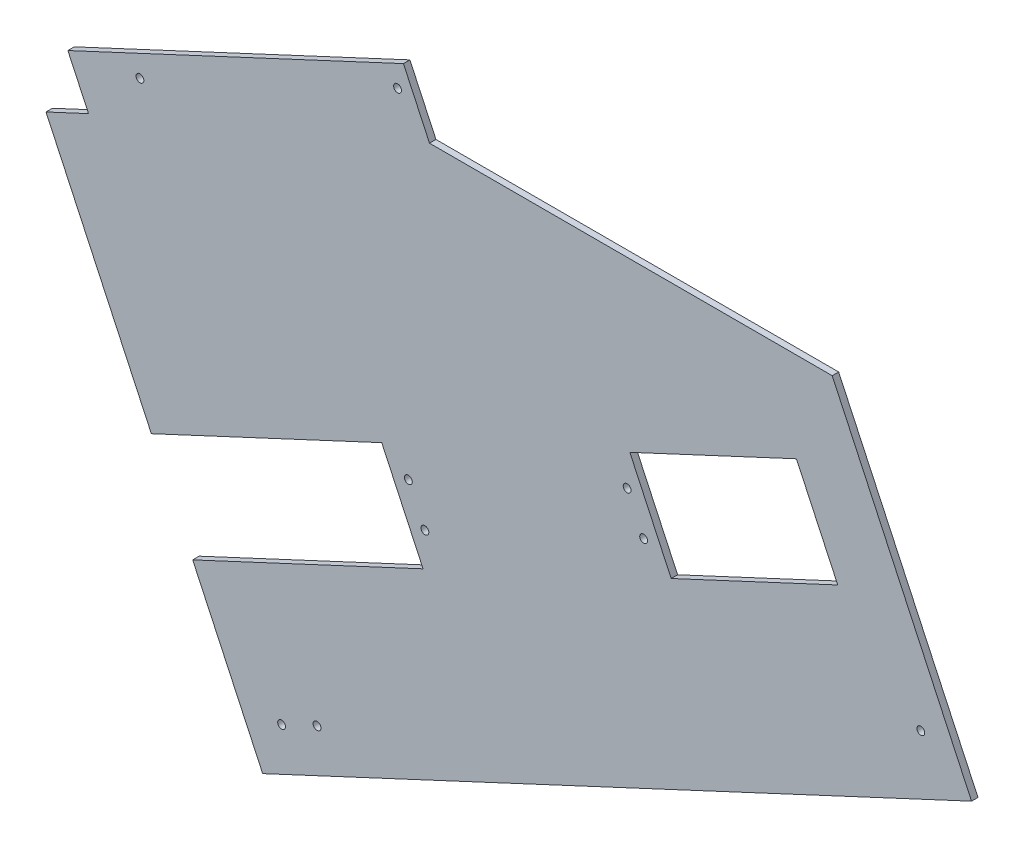
SolidWorks part; units mm, degrees
material "Balsa"
ref_plane "Front Plane" through (0, 0, 0) normal (0, 0, 1) x (1, 0, 0)
ref_plane "Top Plane" through (0, 0, 0) normal (0, 1, 0) x (1, 0, 0)
ref_plane "Right Plane" through (0, 0, 0) normal (1, 0, 0) x (0, 0, -1)
sketch "Sketch1" plane through (0, 0, 0) normal (0, 0, 1) x (1, 0, 0)
  line L0 (327.4362, 0.0035) -> (121.4984, 0.0035)
  line L1 (121.4984, 0.0035) -> (108.169, 28.5884)
  line L2 (108.169, 28.5884) -> (-63.4467, -51.4373)
  line L3 (-63.4467, -51.4373) -> (57.9293, -311.7289) construction
  line L4 (57.9293, -311.7289) -> (398.701, -152.8244)
  line L5 (271.5352, 119.8836) -> (277.3251, 107.4672) construction
  line L6 (190.5834, 136.311) -> (-12.0446, 41.824) construction
  line L7 (-63.4467, -51.4373) -> (255.5737, 97.3243) construction
  line L8 (398.701, -152.8244) -> (327.4362, 0.0035)
  line L9 (57.9293, -311.7289) -> (36.1779, -321.8717)
  line L10 (36.1779, -321.8717) -> (-74.6326, -84.2378)
  line L11 (50.7481, 0) -> (323.7481, 0) construction
  line L12 (-74.6326, -84.2378) -> (-52.8812, -74.095)
  line L13 (-90.9879, -49.1637) -> (-85.1981, -61.5801) construction
  line L14 (-52.8812, -74.095) -> (-63.4467, -51.4373)
  circle A0 centre (162.7613, -40.6644) radius 32.5 construction
  circle A1 centre (336.0773, -108.8767) radius 32.5 construction
  circle A2 centre (90.1802, -40.6644) radius 32.5 construction
  circle A3 centre (232.5481, -40.6644) radius 32.5 construction
  circle A4 centre (207.2768, 100.5118) radius 39.5 construction
  arc A5 (-3.3339, 41.4724) -> (-17.3744, 34.9252) centre (-8.0297, 33.2141) ccw construction
  circle A6 centre (304.5287, -40.6644) radius 32.5 construction
  circle A7 centre (254.9584, -108.8767) radius 32.5 construction
  circle A8 centre (179.3206, -108.8767) radius 32.5 construction
  circle A9 centre (101.4264, -108.8767) radius 32.5 construction
  circle A10 centre (270.383, -163.8108) radius 32.5 construction
  circle A11 centre (372.7594, -134.5783) radius 2
  dimension "D2" = 65
  dimension "D3" = 65
  dimension "D5" = 4
  dimension "D1" = 350
  dimension "D4" = 25
  dimension "24.5/2" = 15.8
  dimension "D6" = 27.5
extrude "Boss-Extrude1" add sketch "Sketch1" along normal up to surface (3.3 mm away)
sketch "Sketch2" plane through (0, 0, 3.3) normal (0, 0, 1) x (1, 0, 0)
  circle A0 centre (105.1447, 16.1444) radius 2
  circle A1 centre (-26.5934, -45.2861) radius 2
  circle A2 centre (-26.5934, -45.2861) radius 2 construction
  circle A3 centre (105.1447, 16.1444) radius 2 construction
extrude "Cut-Extrude1" cut sketch "Sketch2" against normal through all
sketch "Sketch3" plane through (0, 0, 3.3) normal (0, 0, 1) x (1, 0, 0)
  line L2 (398.701, -152.8244) -> (36.1779, -321.8717) construction
  line L3 (36.1779, -321.8717) -> (-74.6326, -84.2378) construction
  circle A0 centre (45.8517, -295.2932) radius 2
  circle A1 centre (63.9779, -286.8408) radius 2
  dimension "D1" = 4
  dimension "D2" = 4
  dimension "D3" = 20
  dimension "D5" = 20
  dimension "D6" = 20
  dimension "D4" = 20
extrude "Cut-Extrude2" cut sketch "Sketch3" against normal blind 4
sketch "Sketch4" plane through (0, 0, 3.3) normal (0, 0, 1) x (1, 0, 0)
  line L0 (330.2782, -91.2744) -> (309.1473, -45.959)
  line L1 (309.1473, -45.959) -> (223.9543, -85.6851)
  line L2 (223.9543, -85.6851) -> (245.0853, -131.0005)
  line L3 (245.0853, -131.0005) -> (330.2782, -91.2744)
  line L4 (309.1473, -45.959) -> (223.9543, -85.6851) construction
  line L5 (245.0853, -131.0005) -> (330.2782, -91.2744) construction
  line L6 (330.2782, -91.2744) -> (309.1473, -45.959) construction
  line L7 (118.2022, -190.1671) -> (97.0712, -144.8517)
  line L8 (97.0712, -144.8517) -> (-20.7488, -199.7921)
  line L9 (-20.7488, -199.7921) -> (0.3821, -245.1075)
  line L10 (0.3821, -245.1075) -> (118.2022, -190.1671)
  line L11 (118.2022, -190.1671) -> (0.3821, -245.1075) construction
  line L12 (-20.7488, -199.7921) -> (97.0712, -144.8517) construction
  line L13 (97.0712, -144.8517) -> (118.2022, -190.1671) construction
extrude "Cut-Extrude3" cut sketch "Sketch4" against normal blind 10
sketch "Sketch5" plane through (0, 0, 3.3) normal (0, 0, 1) x (1, 0, 0)
  circle A0 centre (231.009, -120.4069) radius 2
  circle A1 centre (222.5566, -102.2807) radius 2
  circle A2 centre (119.135, -172.5746) radius 2
  circle A3 centre (110.6826, -154.4484) radius 2
  circle A4 centre (119.135, -172.5746) radius 2 construction
  circle A7 centre (110.6826, -154.4484) radius 2 construction
  circle A8 centre (222.5566, -102.2807) radius 2 construction
  circle A9 centre (231.009, -120.4069) radius 2 construction
extrude "Cut-Extrude4" cut sketch "Sketch5" against normal blind 10
